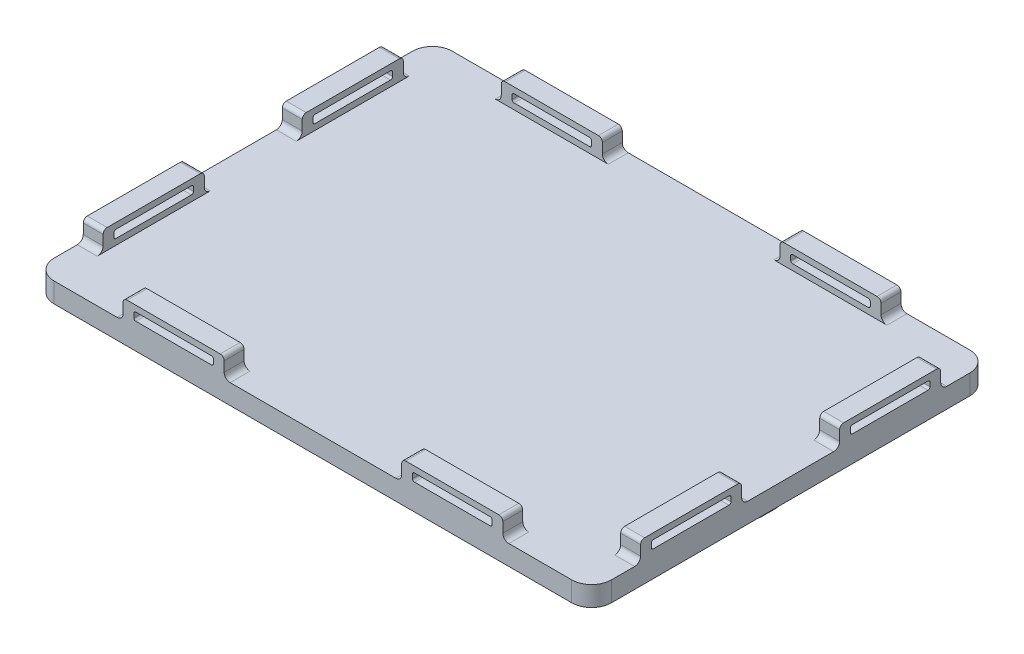
SolidWorks part; units mm, degrees
ref_plane "Front Plane" through (0, 0, 0) normal (0, 0, 1) x (1, 0, 0)
ref_plane "Top Plane" through (0, 0, 0) normal (0, 1, 0) x (1, 0, 0)
ref_plane "Right Plane" through (0, 0, 0) normal (1, 0, 0) x (0, 0, -1)
sketch "Sketch1" plane through (0, 0, 0) normal (0, 1, 0) x (1, 0, 0)
  line L1 (5, 0) -> (135, 0)
  line L2 (0, 5) -> (0, 95)
  line L3 (5, 100) -> (135, 100)
  line L4 (140, 5) -> (140, 95)
  arc A0 (5, 0) -> (0, 5) centre (5, 5) cw
  arc A1 (135, 0) -> (140, 5) centre (135, 5) ccw
  arc A2 (135, 100) -> (140, 95) centre (135, 95) cw
  arc A3 (0, 95) -> (5, 100) centre (5, 95) cw
  point P7 (0, 0)
  point P10 (140, 0)
  point P13 (140, 100)
  dimension "D3" = 5
  dimension "D1" = 140
  dimension "D2" = 100
extrude "Boss-Extrude1" add sketch "Sketch1" along normal blind 5
sketch "Sketch2" plane through (0, 0, 0) normal (0, -1, 0) x (1, 0, 0)
  line L0 (5, 0) -> (135, 0) construction
  line L1 (12, -42) -> (16, -42)
  line L2 (12, -42) -> (12, -51)
  line L3 (12, -51) -> (16, -51)
  line L4 (16, -42) -> (16, -51)
  line L5 (119, -55) -> (128, -55)
  line L6 (119, -55) -> (119, -59)
  line L7 (119, -59) -> (128, -59)
  line L8 (128, -55) -> (128, -59)
  line L11 (0, -95) -> (0, -5) construction
  line L12 (140, -5) -> (140, -95) construction
  dimension "D1" = 9
  dimension "D2" = 4
  dimension "D3" = 9
  dimension "D4" = 4
  dimension "D5" = 12
  dimension "D6" = 12
  dimension "D7" = 42
  dimension "D8" = 55
extrude "Boss-Extrude2" add sketch "Sketch2" along normal blind 13
sketch "Sketch3" plane through (0, 5, 0) normal (0, 1, 0) x (1, 0, 0)
  line L10 (0, 95) -> (0, 5) construction
  line L11 (0, 87.7) -> (5, 87.7)
  line L12 (0, 87.7) -> (0, 62.3)
  line L23 (70, 100) -> (70, 0) construction
  line L24 (135, 100) -> (5, 100) construction
  line L25 (5, 0) -> (135, 0) construction
  line L26 (0, 62.3) -> (5, 62.3)
  line L27 (5, 87.7) -> (5, 62.3)
  line L28 (140, 5) -> (140, 95) construction
  line L29 (0, 37.7) -> (5, 37.7)
  line L30 (0, 37.7) -> (0, 12.3)
  line L31 (0, 12.3) -> (5, 12.3)
  line L32 (5, 37.7) -> (5, 12.3)
  line L33 (140, 87.7) -> (135, 87.7)
  line L34 (140, 87.7) -> (140, 62.3)
  line L35 (140, 62.3) -> (135, 62.3)
  line L36 (135, 87.7) -> (135, 62.3)
  line L37 (0, 50) -> (140, 50) construction
  line L38 (140, 37.7) -> (135, 37.7)
  line L39 (140, 37.7) -> (140, 12.3)
  line L40 (140, 12.3) -> (135, 12.3)
  line L41 (135, 37.7) -> (135, 12.3)
  line L43 (22.3, 100) -> (47.7, 100)
  line L44 (22.3, 100) -> (22.3, 95)
  line L45 (22.3, 95) -> (47.7, 95)
  line L46 (47.7, 100) -> (47.7, 95)
  line L47 (92.3, 100) -> (117.7, 100)
  line L48 (92.3, 100) -> (92.3, 95)
  line L49 (92.3, 95) -> (117.7, 95)
  line L50 (117.7, 100) -> (117.7, 95)
  line L51 (22.3, 0) -> (47.7, 0)
  line L52 (22.3, 0) -> (22.3, 5)
  line L53 (22.3, 5) -> (47.7, 5)
  line L54 (47.7, 0) -> (47.7, 5)
  line L55 (92.3, 0) -> (117.7, 0)
  line L56 (92.3, 0) -> (92.3, 5)
  line L57 (92.3, 5) -> (117.7, 5)
  line L58 (117.7, 0) -> (117.7, 5)
  dimension "D1" = 25.4
  dimension "D2" = 5
  dimension "D3" = 5
  dimension "D4" = 5
  dimension "D5" = 5
  dimension "D6" = 5
  dimension "D7" = 5
  dimension "D8" = 5
  dimension "D9" = 25.4
  dimension "D10" = 5
  dimension "D11" = 25.4
  dimension "D12" = 25.4
  dimension "D13" = 12.3
  dimension "D14" = 12.3
  dimension "D15" = 12.3
  dimension "D16" = 12.3
  dimension "D17" = 25.4
  dimension "D18" = 25.4
  dimension "D19" = 25.4
  dimension "D20" = 25.4
  dimension "D21" = 22.3
  dimension "D22" = 22.3
  dimension "D23" = 22.3
  dimension "D24" = 22.3
extrude "Boss-Extrude3" add sketch "Sketch3" along normal blind 5
sketch "Sketch4" plane through (0, 0, 0) normal (-1, 0, 0) x (0, 0, 1)
  line L0 (-87.7, 5) -> (-62.3, 5) construction
  line L1 (-87.7, 7.5) -> (-62.3, 7.5) construction
  line L2 (-84.5, 8.5) -> (-65.5, 8.5)
  line L3 (-85, 8) -> (-85, 7)
  line L4 (-84.5, 6.5) -> (-65.5, 6.5)
  line L5 (-65, 8) -> (-65, 7)
  line L6 (-87.7, 10) -> (-87.7, 5) construction
  line L7 (-62.3, 10) -> (-62.3, 5) construction
  line L8 (-85, 7.5) -> (-65, 7.5) construction
  line L9 (-75, 10) -> (-75, 5) construction
  line L10 (-87.7, 10) -> (-62.3, 10) construction
  line L11 (-75, 8.5) -> (-75, 6.5) construction
  line L12 (-37.7, 5) -> (-12.3, 5) construction
  line L13 (-35, 7.5) -> (-15, 7.5) construction
  line L14 (-34.5, 8.5) -> (-15.5, 8.5)
  line L15 (-35, 8) -> (-35, 7)
  line L16 (-34.5, 6.5) -> (-15.5, 6.5)
  line L17 (-15, 8) -> (-15, 7)
  line L18 (-25, 8.5) -> (-25, 6.5) construction
  line L19 (-37.7, 7.5) -> (-12.3, 7.5) construction
  line L20 (-37.7, 10) -> (-37.7, 5) construction
  line L21 (-12.3, 10) -> (-12.3, 5) construction
  line L22 (-25, 10) -> (-25, 5) construction
  line L23 (-37.7, 10) -> (-12.3, 10) construction
  arc A0 (-65.5, 8.5) -> (-65, 8) centre (-65.5, 8) cw
  arc A1 (-65.5, 6.5) -> (-65, 7) centre (-65.5, 7) ccw
  arc A2 (-85, 7) -> (-84.5, 6.5) centre (-84.5, 7) ccw
  arc A3 (-84.5, 8.5) -> (-85, 8) centre (-84.5, 8) ccw
  arc A4 (-15.5, 6.5) -> (-15, 7) centre (-15.5, 7) ccw
  arc A5 (-15.5, 8.5) -> (-15, 8) centre (-15.5, 8) cw
  arc A6 (-35, 7) -> (-34.5, 6.5) centre (-34.5, 7) ccw
  arc A7 (-34.5, 8.5) -> (-35, 8) centre (-34.5, 8) ccw
  point P22 (-75, 7.5)
  point P23 (-75, 7.5)
  point P26 (-65, 8.5)
  point P31 (-85, 6.5)
  point P34 (-85, 8.5)
  point P57 (-25, 7.5)
  point P58 (-25, 7.5)
  point P63 (-15, 8.5)
  point P66 (-35, 6.5)
  point P69 (-35, 8.5)
  dimension "D3" = 0.5
  dimension "D6" = 0.5
  dimension "D1" = 20
  dimension "D2" = 2
  dimension "D4" = 20
  dimension "D5" = 2
extrude "Cut-Extrude1" cut sketch "Sketch4" against normal through all
sketch "Sketch8" plane through (0, 0, 0) normal (0, 0, 1) x (1, 0, 0)
  line L0 (22.3, 5) -> (47.7, 5) construction
  line L1 (22.3, 7.5) -> (47.7, 7.5) construction
  line L2 (22.3, 10) -> (22.3, 5) construction
  line L3 (47.7, 10) -> (47.7, 5) construction
  line L4 (35, 10) -> (35, 5) construction
  line L5 (22.3, 10) -> (47.7, 10) construction
  line L6 (92.3, 5) -> (117.7, 5) construction
  line L7 (92.3, 7.5) -> (117.7, 7.5) construction
  line L8 (92.3, 10) -> (92.3, 5) construction
  line L9 (117.7, 10) -> (117.7, 5) construction
  line L10 (105, 10) -> (105, 5) construction
  line L11 (92.3, 10) -> (117.7, 10) construction
  line L12 (25, 7.5) -> (45, 7.5) construction
  line L13 (25.5, 8.5) -> (44.5, 8.5)
  line L14 (25, 8) -> (25, 7)
  line L15 (25.5, 6.5) -> (44.5, 6.5)
  line L16 (45, 8) -> (45, 7)
  line L17 (95.5, 8.5) -> (114.5, 8.5)
  line L18 (95, 8) -> (95, 7)
  line L19 (95.5, 6.5) -> (114.5, 6.5)
  line L20 (115, 8) -> (115, 7)
  line L21 (35, 8.5) -> (35, 6.5) construction
  line L22 (95, 7.5) -> (115, 7.5) construction
  line L23 (105, 8.5) -> (105, 6.5) construction
  arc A0 (114.5, 6.5) -> (115, 7) centre (114.5, 7) ccw
  arc A1 (114.5, 8.5) -> (115, 8) centre (114.5, 8) cw
  arc A2 (95, 7) -> (95.5, 6.5) centre (95.5, 7) ccw
  arc A3 (95.5, 8.5) -> (95, 8) centre (95.5, 8) ccw
  arc A4 (44.5, 6.5) -> (45, 7) centre (44.5, 7) ccw
  arc A5 (44.5, 8.5) -> (45, 8) centre (44.5, 8) cw
  arc A6 (25, 7) -> (25.5, 6.5) centre (25.5, 7) ccw
  arc A7 (25.5, 8.5) -> (25, 8) centre (25.5, 8) ccw
  point P40 (35, 7.5)
  point P41 (35, 7.5)
  point P46 (105, 7.5)
  point P47 (105, 7.5)
  point P50 (115, 6.5)
  point P53 (115, 8.5)
  point P58 (95, 8.5)
  point P63 (45, 8.5)
  point P66 (25, 6.5)
  point P69 (25, 8.5)
  dimension "D5" = 0.5
  dimension "D1" = 20
  dimension "D2" = 2
  dimension "D3" = 20
  dimension "D4" = 2
extrude "Cut-Extrude2" cut sketch "Sketch8" against normal through all
fillet "Fillet1" radius 1 16 edges at (137.5, 10, -87.7) (137.5, 10, -62.3) (2.5, 10, -62.3) (2.5, 10, -87.7) (22.3, 10, -97.5) (47.7, 10, -97.5) (137.5, 10, -37.7) (137.5, 10, -12.3) (2.5, 10, -37.7) (2.5, 10, -12.3) (117.7, 10, -97.5) (92.3, 10, -97.5) (117.7, 10, -2.5) (92.3, 10, -2.5) (47.7, 10, -2.5) (22.3, 10, -2.5)
fillet "Fillet2" radius 1.5 16 edges at (22.3, 5, -97.5) (47.7, 5, -97.5) (137.5, 5, -62.3) (137.5, 5, -87.7) (2.5, 5, -87.7) (2.5, 5, -62.3) (137.5, 5, -37.7) (137.5, 5, -12.3) (2.5, 5, -37.7) (2.5, 5, -12.3) (117.7, 5, -97.5) (92.3, 5, -97.5) (117.7, 5, -2.5) (92.3, 5, -2.5) (47.7, 5, -2.5) (22.3, 5, -2.5)
sketch "Sketch6" plane through (12, 0, 0) normal (-1, 0, 0) x (0, 0, 1)
  line L0 (-46.5, 0) -> (-46.5, -13) construction
  line L1 (-42, 0) -> (-51, 0) construction
  line L2 (-42, -13) -> (-51, -13) construction
  circle A1 centre (-46.5, -9) radius 1.55
  dimension "D1" = 3.1
  dimension "D2" = 4
extrude "Cut-Extrude3" cut sketch "Sketch6" against normal blind 5
sketch "Sketch7" plane through (0, 0, -55) normal (0, 0, 1) x (1, 0, 0)
  line L0 (123.5, 0) -> (123.5, -13) construction
  line L1 (128, 0) -> (119, 0) construction
  line L2 (128, -13) -> (119, -13) construction
  circle A1 centre (123.5, -9) radius 1.55
  dimension "D1" = 3.1
  dimension "D2" = 4
extrude "Cut-Extrude4" cut sketch "Sketch7" against normal blind 5
fillet "Fillet3" radius 1.5 4 edges at (128, -13, -57) (119, -13, -57) (14, -13, -42) (14, -13, -51)
fillet "Fillet4" radius 1.5 4 edges at (128, 0, -57) (119, 0, -57) (14, 0, -42) (14, 0, -51)
